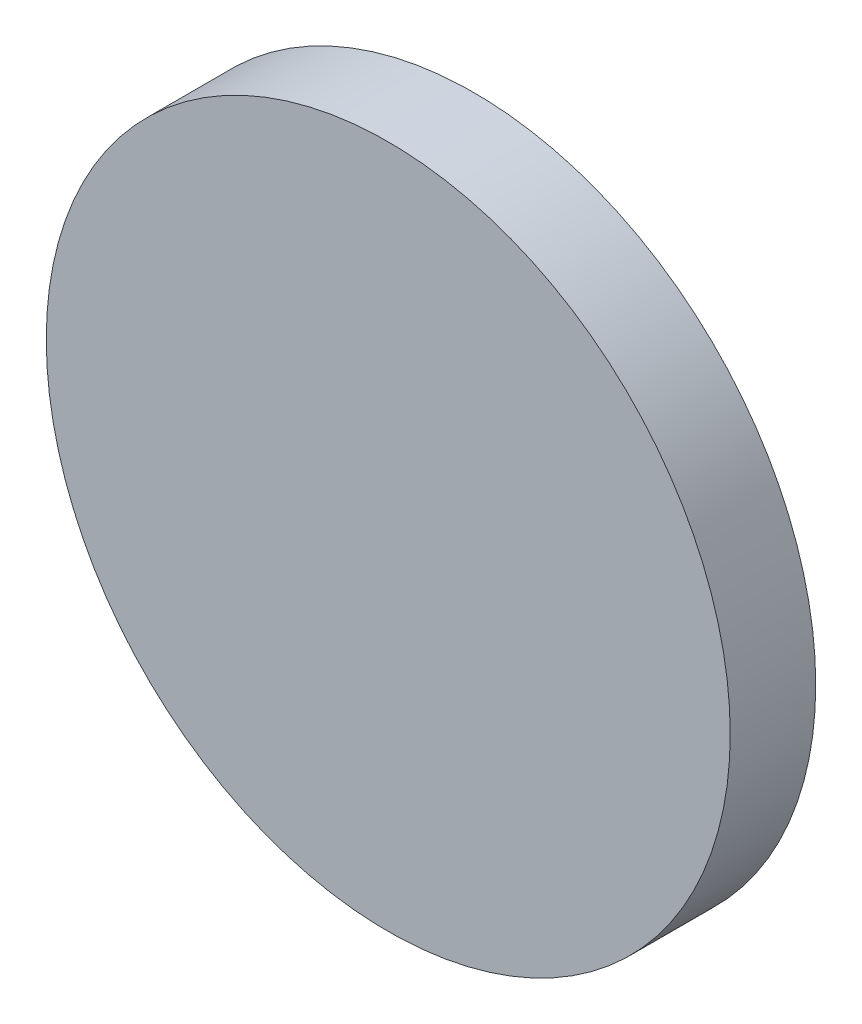
SolidWorks part; units mm, degrees
ref_plane "前视基准面" through (0, 0, 0) normal (0, 0, 1) x (1, 0, 0)
ref_plane "上视基准面" through (0, 0, 0) normal (0, 1, 0) x (1, 0, 0)
ref_plane "右视基准面" through (0, 0, 0) normal (1, 0, 0) x (0, 0, -1)
sketch "草图1" plane through (0, 0, 0) normal (0, 0, 1) x (1, 0, 0)
  circle A0 centre (0, 0) radius 20
extrude "凸台-拉伸1" add sketch "草图1" along normal blind 5
ref_point "点2"
ref_point "点4"
sketch "草图2" plane through (0, 0, 5) normal (0, 0, 1) x (1, 0, 0)
  line L0 (0, 0) -> (0, 20)
sketch "草图3" plane through (0, 0, 0) normal (0, 0, -1) x (-1, 0, 0)
  line L0 (0, 0) -> (0, 20)
ref_axis "基准轴1" through (0, 0, 5) along (0, 1, 0)
ref_axis "基准轴2" through (0, 0, 0) along (0, 1, 0)
ref_axis "基准轴3" through (0, 0, 0) along (0, 0, -1)
ref_axis "基准轴4" through (0, 0, 5) along (0, 0, 1)
